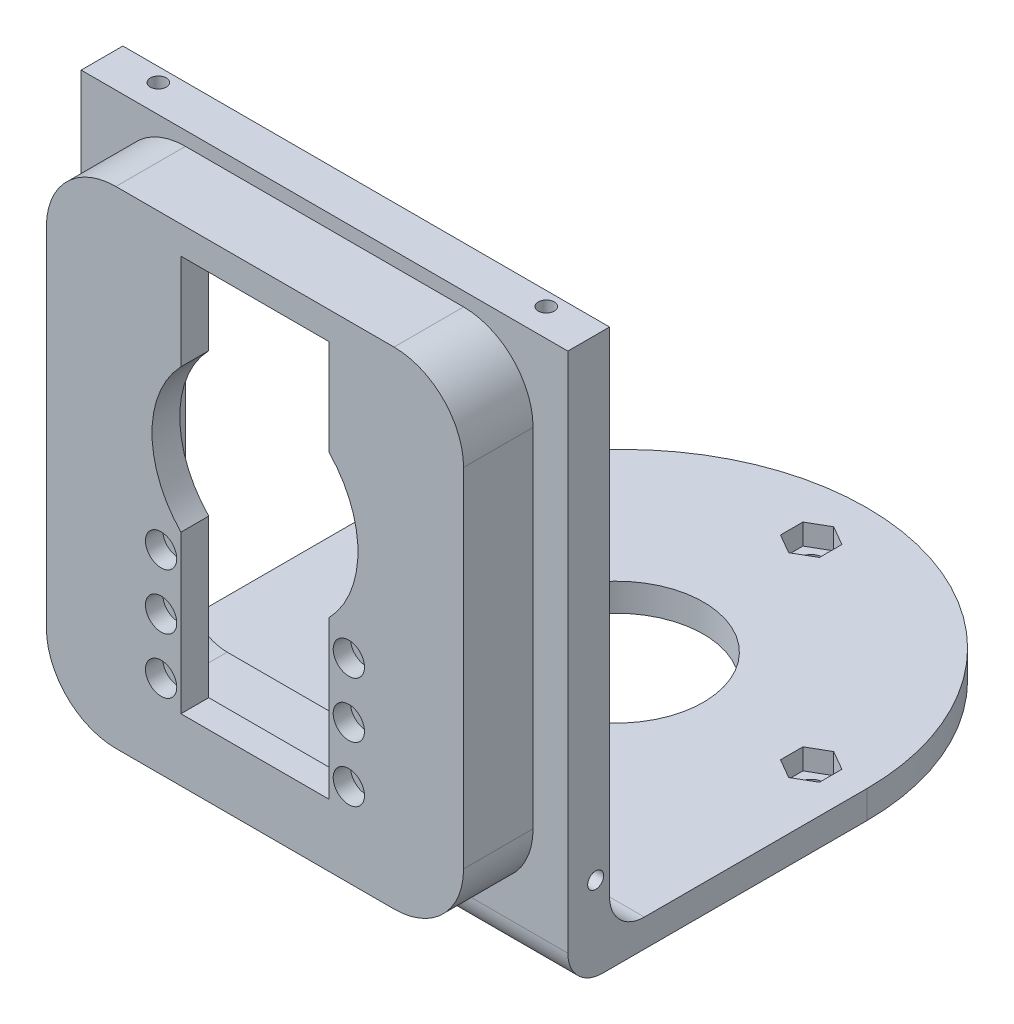
SolidWorks part; units mm, degrees
ref_plane "Front Plane" through (0, 0, 0) normal (0, 0, 1) x (1, 0, 0)
ref_plane "Top Plane" through (0, 0, 0) normal (0, 1, 0) x (1, 0, 0)
ref_plane "Right Plane" through (0, 0, 0) normal (1, 0, 0) x (0, 0, -1)
sketch "Sketch1" plane through (0, 0, 0) normal (0, 0, 1) x (1, 0, 0)
  line L1 (-20, -35) -> (20, -35)
  line L2 (-30, -25) -> (-30, 25)
  line L3 (-20, 35) -> (20, 35)
  line L4 (30, -25) -> (30, 25)
  line L5 (-30, -35) -> (30, 35) construction
  line L6 (-30, 35) -> (30, -35) construction
  arc A1 (20, 35) -> (30, 25) centre (20, 25) cw
  arc A2 (20, -35) -> (30, -25) centre (20, -25) ccw
  arc A3 (-20, -35) -> (-30, -25) centre (-20, -25) cw
  arc A4 (-30, 25) -> (-20, 35) centre (-20, 25) cw
  point P0 (0, 0)
  dimension "D1" = 60
  dimension "D3" = 10
  dimension "D2" = 70
extrude "Boss-Extrude1" add sketch "Sketch1" against normal blind 10
ref_plane "Plane1" through (60, 0, 0) normal (1, 0, 0) x (0, 0, -1)
ref_plane "Plane2" through (60, 0, 0) normal (1, 0, 0) x (0, 0, -1)
sketch "Sketch10" plane through (0, 0, -10) normal (0, 0, -1) x (-1, 0, 0)
  line L0 (0, -3) -> (0, 0) construction
  line L1 (-35, -43) -> (35, -43)
  line L2 (-35, -43) -> (-35, 37)
  line L3 (-35, 37) -> (35, 37)
  line L4 (35, -43) -> (35, 37)
  line L5 (-35, -43) -> (35, 37) construction
  line L6 (-35, 37) -> (35, -43) construction
  point P0 (0, -3)
  dimension "D3" = 3
  dimension "D1" = 80
  dimension "D2" = 70
extrude "Boss-Extrude6" add sketch "Sketch10" along normal blind 78
sketch "Sketch14" plane through (0, 0, 0) normal (0, 0, 1) x (1, 0, 0)
  line L8 (20, 31) -> (-20, 31)
  line L9 (26, -25) -> (26, 25)
  line L10 (-20, -31) -> (20, -31)
  line L11 (-26, 25) -> (-26, -25)
  line L12 (20, 31) -> (-20, 31)
  line L13 (26, -25) -> (26, 25)
  line L14 (-20, -31) -> (20, -31)
  line L15 (-26, 25) -> (-26, -25)
  arc A10 (26, 25) -> (20, 31) centre (20, 25) ccw
  arc A11 (20, -31) -> (26, -25) centre (20, -25) ccw
  arc A12 (-26, -25) -> (-20, -31) centre (-20, -25) ccw
  arc A13 (-20, 31) -> (-26, 25) centre (-20, 25) ccw
  arc A14 (26, 25) -> (20, 31) centre (20, 25) ccw
  arc A15 (20, -31) -> (26, -25) centre (20, -25) ccw
  arc A16 (-26, -25) -> (-20, -31) centre (-20, -25) ccw
  arc A17 (-20, 31) -> (-26, 25) centre (-20, 25) ccw
  dimension "D1" = 4
extrude "Cut-Extrude7" cut sketch "Sketch14" against normal blind 46
sketch "Sketch15" plane through (0, 0, 0) normal (0, 0, 1) x (1, 0, 0)
  line L0 (0, 0) -> (0, -17.9719) construction
  line L1 (-20, 31) -> (-10.65, 31)
  line L2 (-10.65, 31) -> (-10.65, -26)
  line L3 (-10.65, -26) -> (10.65, -26)
  line L4 (10.65, -26) -> (10.65, 31)
  line L5 (10.65, 31) -> (20, 31)
  line L10 (0, 0) -> (13.5, 0) construction
  line L11 (13.5, 0) -> (13.5, -7) construction
  line L12 (13.5, -7) -> (13.5, -15) construction
  line L13 (13.5, -15) -> (13.5, -23) construction
  line L14 (-20, -31) -> (20, -31) construction
  line L15 (-20, -31) -> (20, -31)
  line L18 (20, 31) -> (-20, 31) construction
  line L19 (-26, 25) -> (-26, -25) construction
  line L20 (-26, 25) -> (-26, -25)
  line L21 (26, -25) -> (26, 25) construction
  line L22 (26, -25) -> (26, 25)
  circle A0 centre (0, 0) radius 11 construction
  circle A1 centre (13.5, -7) radius 1.25
  circle A3 centre (13.5, -15) radius 1.25
  circle A4 centre (13.5, -23) radius 1.25
  circle A5 centre (-13.5, -7) radius 1.25
  circle A6 centre (-13.5, -15) radius 1.25
  circle A7 centre (-13.5, -23) radius 1.25
  arc A8 (-20, 31) -> (-26, 25) centre (-20, 25) ccw construction
  arc A9 (-26, -25) -> (-20, -31) centre (-20, -25) ccw
  arc A10 (26, -25) -> (20, -31) centre (20, -25) cw
  arc A11 (-20, 31) -> (-26, 25) centre (-20, 25) ccw
  arc A12 (26, 25) -> (20, 31) centre (20, 25) ccw construction
  arc A13 (26, 25) -> (20, 31) centre (20, 25) ccw
  point P5 (0, -26)
  dimension "D1" = 22
  dimension "D5" = 2.5
  dimension "D2" = 21.3
  dimension "D3" = 13.5
  dimension "D4" = 7
  dimension "D6" = 8
  dimension "D7" = 8
  dimension "D9" = 5
extrude "Boss-Extrude7" add sketch "Sketch15" against normal blind 4
sketch "Sketch17" plane through (0, 0, 0) normal (0, 0, 1) x (1, 0, 0)
  circle A0 centre (-13.5, -7) radius 2.25
  circle A1 centre (-13.5, -15) radius 2.25
  circle A2 centre (-13.5, -23) radius 2.25
  circle A3 centre (13.5, -7) radius 2.25
  circle A4 centre (13.5, -15) radius 2.25
  circle A5 centre (13.5, -23) radius 2.25
  dimension "D1" = 4.5
extrude "Cut-Extrude9" cut sketch "Sketch17" against normal blind 2.5
sketch "Sketch19" plane through (35, 0, 0) normal (1, 0, 0) x (0, 0, -1)
  line L0 (88, -43) -> (10, -43) construction
  line L1 (88, 37) -> (16, 37)
  line L2 (88, 37) -> (88, -39)
  line L3 (88, -39) -> (16, -39)
  line L4 (16, 37) -> (16, -39)
  line L5 (10, 37) -> (10, -43) construction
  dimension "D1" = 4
  dimension "D2" = 6
extrude "Cut-Extrude11" cut sketch "Sketch19" against normal blind 70
sketch "Sketch20" plane through (0, -43, 0) normal (0, -1, 0) x (1, 0, 0)
  line L0 (-35, -16) -> (35, -88) construction
  line L1 (28, -52) -> (0, -52) construction
  circle A0 centre (28, -52) radius 1.65
  circle A1 centre (0, -80) radius 1.65
  circle A2 centre (-28, -52) radius 1.65
  circle A4 centre (0, -24) radius 1.65 [skipped]
  point P6 (0, -52)
  point P16 (0, -52)
  dimension "D1" = 3.3
  dimension "D3" = 28
  dimension "D2" = 4
extrude "Cut-Extrude12" cut sketch "Sketch20" against normal blind 10
sketch "Sketch21" plane through (0, -39, 0) normal (0, 1, 0) x (1, 0, 0)
  line L0 (-28, 52) -> (28, 52) construction
  circle A0 centre (0, 52) radius 12.5
  dimension "D1" = 25
extrude "Cut-Extrude13" cut sketch "Sketch21" against normal blind 10
fillet "Fillet2" [suppressed] radius 20
sketch "Sketch22" plane through (0, -39, 0) normal (0, 1, 0) x (1, 0, 0)
  line L1 (0, 83.2332) -> (-2.8, 81.6166)
  line L2 (-2.8, 81.6166) -> (-2.8, 78.3834)
  line L3 (-2.8, 78.3834) -> (0, 76.7668)
  line L4 (0, 76.7668) -> (2.8, 78.3834)
  line L5 (2.8, 78.3834) -> (2.8, 81.6166)
  line L6 (2.8, 81.6166) -> (0, 83.2332)
  line L7 (-30.8, 50.3834) -> (-28, 48.7668)
  line L8 (-28, 48.7668) -> (-25.2, 50.3834)
  line L9 (-25.2, 50.3834) -> (-25.2, 53.6166)
  line L10 (-25.2, 53.6166) -> (-28, 55.2332)
  line L11 (-28, 55.2332) -> (-30.8, 53.6166)
  line L12 (-30.8, 53.6166) -> (-30.8, 50.3834)
  line L19 (28, 55.2332) -> (25.2, 53.6166)
  line L20 (25.2, 53.6166) -> (25.2, 50.3834)
  line L21 (25.2, 50.3834) -> (28, 48.7668)
  line L22 (28, 48.7668) -> (30.8, 50.3834)
  line L23 (30.8, 50.3834) -> (30.8, 53.6166)
  line L24 (30.8, 53.6166) -> (28, 55.2332)
  circle A0 centre (0, 80) radius 2.8 construction
  circle A1 centre (-28, 52) radius 2.8 construction
  circle A3 centre (28, 52) radius 2.8 construction
  dimension "D1" = 5.6
extrude "Cut-Extrude14" cut sketch "Sketch22" against normal blind 3
fillet "Fillet3" radius 5 2 edges at (0, -43, -10) (0, -39, -16)
sketch "Sketch23" plane through (0, 0, -16) normal (0, 0, -1) x (-1, 0, 0)
  line L0 (-31, -28.8) -> (-31, -33)
  line L1 (-31, -28.8) -> (-29, -28.8)
  line L2 (-29, -28.8) -> (-29, -33)
  line L3 (-31, -33) -> (-29, -33)
  line L4 (-35, 37) -> (-35, -34) construction
  line L6 (35, -39) -> (-35, -39) construction
  dimension "D1" = 4.2
  dimension "D2" = 2
  dimension "D3" = 6
  dimension "D4" = 6
extrude "Cut-Extrude15" cut sketch "Sketch23" against normal blind 4
sketch "Sketch24" plane through (29, 0, 0) normal (1, 0, 0) x (0, 0, -1)
  line L0 (16, -33) -> (12, -28.8) construction
  circle A0 centre (14, -30.9) radius 1.15
  dimension "D1" = 2.3
extrude "Cut-Extrude16" cut sketch "Sketch24" along normal through all
mirror "Mirror1" about plane through (0, 0, 0) normal (1, 0, 0) of "Cut-Extrude15", "Cut-Extrude16"
sketch "Sketch27" plane through (0, 0, -16) normal (0, 0, -1) x (-1, 0, 0)
  line L0 (35, 31) -> (-35, 31) construction
  line L1 (30, 31) -> (30, 33)
  line L2 (30, 31) -> (25.8, 31)
  line L3 (25.8, 31) -> (25.8, 33)
  line L4 (30, 33) -> (25.8, 33)
  line L5 (-25.8, 31) -> (-25.8, 33)
  line L6 (-25.8, 31) -> (-30, 31)
  line L7 (-30, 31) -> (-30, 33)
  line L8 (-25.8, 33) -> (-30, 33)
  line L9 (0, 31) -> (0, 37) construction
  line L10 (35, 37) -> (-35, 37) construction
  line L11 (35, 37) -> (35, -34) construction
  dimension "D1" = 2
  dimension "D2" = 4.2
  dimension "D3" = 6
  dimension "D4" = 5
extrude "Cut-Extrude17" cut sketch "Sketch27" against normal blind 4
sketch "Sketch28" plane through (0, 31, 0) normal (0, 1, 0) x (1, 0, 0)
  line L0 (-30, 16) -> (-25.8, 12) construction
  circle A0 centre (-27.9, 14) radius 1.15
  dimension "D1" = 2.3
extrude "Cut-Extrude18" cut sketch "Sketch28" along normal through all
mirror "Mirror2" about plane through (0, 0, 0) normal (1, 0, 0) of "Cut-Extrude18"
fillet "Fillet4" radius 35 2 edges at (35, -41, -88) (-35, -41, -88)
sketch "Sketch29" plane through (0, 0, 0) normal (0, 0, 1) x (1, 0, 0)
  circle A0 centre (0, 6.9186) radius 14.8145
extrude "Cut-Extrude19" cut sketch "Sketch29" against normal blind 4
